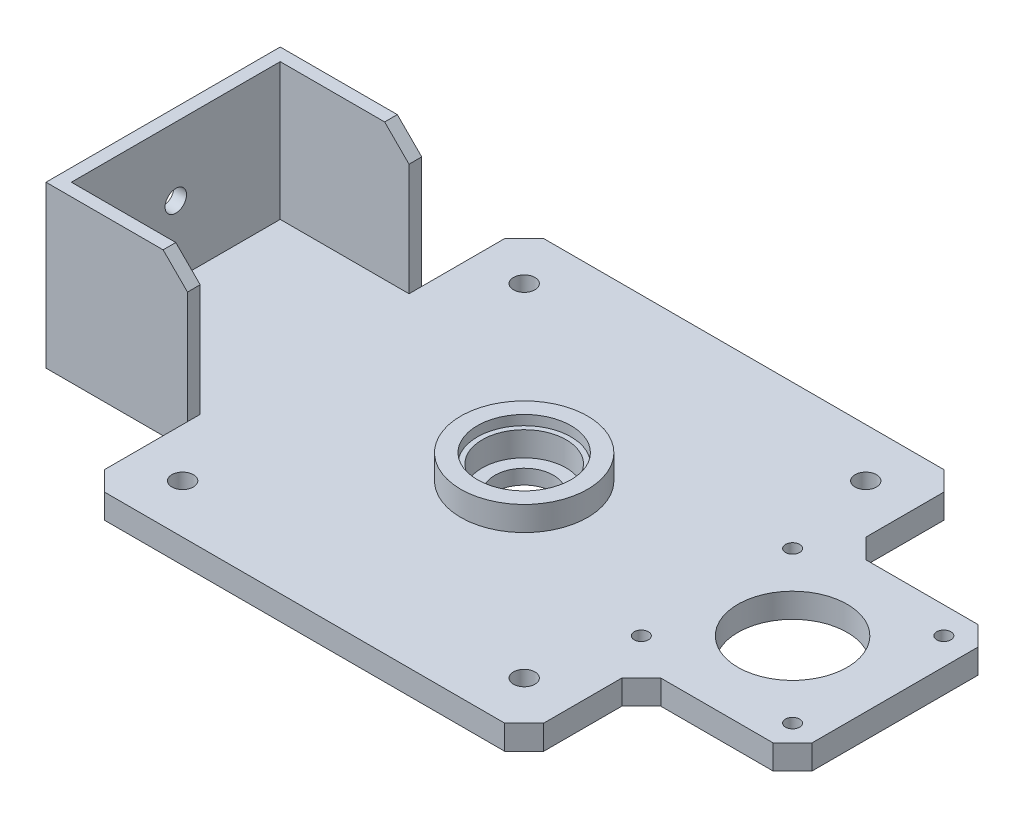
SolidWorks part; units mm, degrees
ref_plane "Front Plane" through (0, 0, 0) normal (0, 0, 1) x (1, 0, 0)
ref_plane "Top Plane" through (0, 0, 0) normal (0, 1, 0) x (1, 0, 0)
ref_plane "Right Plane" through (0, 0, 0) normal (1, 0, 0) x (0, 0, -1)
sketch "Sketch1" plane through (0, 0, 0) normal (0, 1, 0) x (1, 0, 0)
  line L0 (-134.1176, 0) -> (172.5028, 0) construction
  line L1 (-45, 45) -> (45, 45)
  line L2 (45, 45) -> (45, 21)
  line L3 (45, 21) -> (76, 21)
  line L4 (76, 21) -> (76, -21)
  line L5 (-45, 45) -> (-45, 24)
  line L6 (-45, 24) -> (-74, 24)
  line L7 (-74, 24) -> (-74, -24)
  line L8 (-45, 24) -> (-45, 21.4)
  line L9 (-45, 21.4) -> (-71.4, 21.4)
  line L10 (-71.4, 21.4) -> (-71.4, -21.4)
  line L11 (-45, -21.4) -> (-71.4, -21.4)
  line L12 (-45, -24) -> (-45, -21.4)
  line L13 (-45, -24) -> (-74, -24)
  line L14 (-45, -45) -> (-45, -24)
  line L15 (45, -21) -> (76, -21)
  line L16 (45, -45) -> (45, -21)
  line L17 (-45, -45) -> (45, -45)
  line L18 (0, 88.6779) -> (0, -78.3548) construction
  circle A0 centre (70.5, 15.5) radius 1.45
  circle A1 centre (39.5, 15.5) radius 1.45
  circle A2 centre (35, 35) radius 2.2
  circle A3 centre (-35, 35) radius 2.2
  circle A4 centre (-35, -35) radius 2.2
  circle A5 centre (35, -35) radius 2.2
  circle A6 centre (39.5, -15.5) radius 1.45
  circle A7 centre (70.5, -15.5) radius 1.45
  circle A8 centre (0, 0) radius 6
  circle A9 centre (0, 0) radius 8.6
  circle A10 centre (0, 0) radius 9.6
  circle A11 centre (0, 0) radius 13
  circle A12 centre (55, 0) radius 11.2
  dimension "D6" = 4.4
  dimension "D7" = 12
  dimension "D8" = 17.2
  dimension "D9" = 19.2
  dimension "D10" = 26
  dimension "D14" = 2.9
  dimension "D16" = 2.9
  dimension "D17" = 22.4
  dimension "D1" = 90
  dimension "D2" = 42
  dimension "D3" = 90
  dimension "D4" = 10
  dimension "D5" = 10
  dimension "D11" = 31
  dimension "D12" = 5.5
  dimension "D13" = 5.5
  dimension "D15" = 31
  dimension "D18" = 21
  dimension "D19" = 29
  dimension "D20" = 26.4
  dimension "D21" = 48
  dimension "D22" = 42.8
extrude "Boss-Extrude1" add sketch "Sketch1" along normal blind 5 contours L14 L17 L16 L15 L4 L3 L2 L1 L5 L8 L9 L10 L11 L12 A12 A11 A6 A4 A3 A2 A1 A0 A5 A7 | L13 L12 L11 L10 L9 L8 L6 L7 region at (0, 0, -43.273) region at (-45.5608, 0, -22.7)
extrude "Boss-Extrude2" add sketch "Sketch1<3>" along normal blind 33 contours L13 L12 L11 L10 L9 L8 L6 L7 region at (-45.5608, 0, -22.7)
sketch "Sketch1<3>" plane through (0, 0, 0) normal (0, 1, 0) x (1, 0, 0) same geometry as "Sketch1"
extrude "Boss-Extrude3" add sketch "Sketch1<4>" along normal blind 3 contours A11 A10 | A10 A9 | A9 A8 region at (-8.3568, 0, 0) region at (-9.3285, 0, 0) region at (-12.6323, 0, 0)
sketch "Sketch1<4>" plane through (0, 0, 0) normal (0, 1, 0) x (1, 0, 0) same geometry as "Sketch1"
extrude "Boss-Extrude4" add sketch "Sketch1<5>" along normal blind 8 contours A10 A9 | A11 A10 region at (-9.3285, 0, 0) region at (-12.6323, 0, 0)
sketch "Sketch1<5>" plane through (0, 0, 0) normal (0, 1, 0) x (1, 0, 0) same geometry as "Sketch1"
extrude "Boss-Extrude5" add sketch "Sketch1<6>" along normal blind 10 contours A11 A10 region at (-12.6323, 0, 0)
sketch "Sketch1<6>" plane through (0, 0, 0) normal (0, 1, 0) x (1, 0, 0) same geometry as "Sketch1"
sketch "Sketch2" plane through (-71.4, 0, 0) normal (1, 0, 0) x (0, 0, -1)
  line L0 (0, -15.4248) -> (0, 46.2397) construction
  line L1 (21.4, 33) -> (-21.4, 33) construction
  circle A0 centre (0, 19) radius 2.2
  dimension "D2" = 4.4
  dimension "D1" = 14
extrude "Cut-Extrude1" cut sketch "Sketch2" against normal blind 10
chamfer "Chamfer1" distance 4 8 edges at (-45, 2.5, 45) (-45, 2.5, -45) (45, 2.5, -45) (45, 2.5, -21) (76, 2.5, -21) (76, 2.5, 21) (45, 2.5, 21) (45, 2.5, 45)
chamfer "Chamfer2" distance 5 2 edges at (-45, 33, -22.7) (-45, 33, 22.7)
